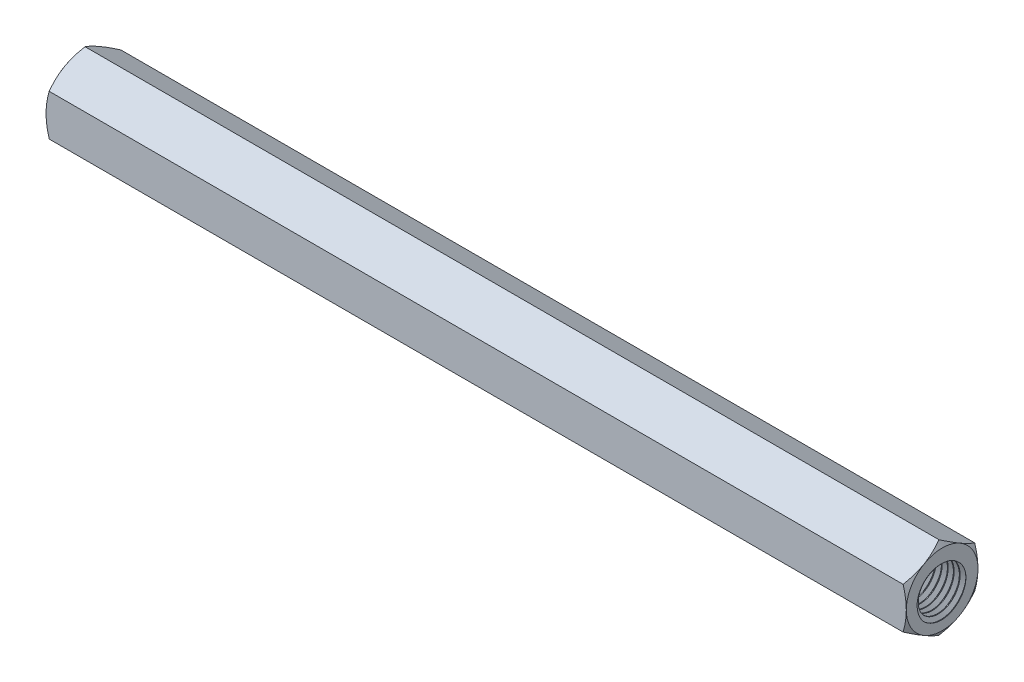
SolidWorks part; units mm, degrees
note: '?' marks a value the reader was unsure of.
ref_plane "Front Plane" through (0, 0, 0) normal (0, 0, 1) x (1, 0, 0)
ref_plane "Top Plane" through (0, 0, 0) normal (0, 1, 0) x (1, 0, 0)
ref_plane "Right Plane" through (0, 0, 0) normal (1, 0, 0) x (0, 0, -1)
sketch "Sketch1" plane through (0, 0, 0) normal (0, 0, 1) x (1, 0, 0)
  line L0 (-76.2, 0) -> (76.2, 0) construction
  line L1 (-76.2, 3.9688) -> (-76.2, -3.9688) construction
  line L2 (76.2, 3.9688) -> (76.2, -3.9688) construction
  line L3 (0, 6.35) -> (0, -6.35) construction
  line L4 (57.15, 3.9688) -> (57.15, -3.9688) construction
  line L5 (-57.15, 3.9688) -> (-57.15, -3.9688) construction
  line L6 (-76.2, 3.9688) -> (-57.15, 3.9688) construction
  line L7 (-76.2, -3.9688) -> (-57.15, -3.9688) construction
  line L8 (57.15, -3.9688) -> (76.2, -3.9688) construction
  line L9 (57.15, 3.9688) -> (76.2, 3.9688) construction
  point P7 (-57.15, 0)
  point P8 (57.15, 0)
  point P17 (67.7333, -3.9688)
  dimension "Length" = 152.4
  dimension "D1" = 19.05
  dimension "Thread Size" = 7.9375
  dimension "Rod OD" = 12.7
  dimension "Thread Length" = 19.05
  dimension "D2" = 114.3
  dimension "D5" = 8.4667
sketch "Sketch2" plane through (0, 0, 0) normal (1, 0, 0) x (0, 0, -1)
  line L1 (6.35, 3.6662) -> (0, 7.3323)
  line L2 (0, 7.3323) -> (-6.35, 3.6662)
  line L3 (-6.35, 3.6662) -> (-6.35, -3.6662)
  line L4 (-6.35, -3.6662) -> (0, -7.3323)
  line L5 (0, -7.3323) -> (6.35, -3.6662)
  line L6 (6.35, -3.6662) -> (6.35, 3.6662)
  circle A1 centre (0, 0) radius 6.35 construction
  point P12 (0, 6.35)
extrude "Boss-Extrude1" add sketch "Sketch2" against normal up to vertex (76.2 mm away) and the other way up to vertex (76.2 mm away) up to point (-76.2, 0, 0) other way up to point (76.2, 0, 0)
sketch "Sketch4" plane through (-76.2, 0, 0) normal (-1, 0, 0) x (0, 0, 1)
  circle A0 centre (0, 0) radius 3.9688
extrude "Cut-Extrude1" cut sketch "Sketch4" against normal up to vertex (19.05 mm away) up to point (-57.15, 0, 0)
sketch "Sketch7" plane through (-57.15, 0, 0) normal (-1, 0, 0) x (0, 0, 1)
  circle A1 centre (0, 0) radius 3.9688
  circle A2 centre (0, 0) radius 3.9688
  dimension "D1" = 0
extrude "Cut-Extrude2" cut sketch "Sketch7" against normal through all draft 59
sketch "Sketch5" plane through (-76.2, 0, 0) normal (-1, 0, 0) x (0, 0, 1)
  line L0 (0, 7.3323) -> (6.35, 3.6662) construction
  circle A0 centre (0, 0) radius 6.35
extrude "Cut-Extrude-Thin2" cut sketch "Sketch5" against normal through all draft 60 thin
mirror "Mirror1" about plane through (0, 0, 0) normal (1, 0, 0) of "Cut-Extrude1", "Cut-Extrude-Thin2", "Cut-Extrude2"
sketch "Sketch3" plane through (-76.2, 0, 0) normal (1, 0, 0) x (0, 0, -1)
  circle A0 centre (0, 0) radius 3.9688 construction
  circle A1 centre (0, 0) radius 3.9688
curve "Helix/Spiral1" pitch 1.0583 height 19.05 turns 18 parameters "pitch"=1.0583
sketch "Sketch6" plane through (0, 0, 0) normal (0, 0, 1) x (1, 0, 0)
  line L0 (-77.1922, 3.8542) -> (-76.1339, 3.8542) construction
  line L1 (-76.1339, 3.8542) -> (-76.663, 4.7707) construction
  line L2 (-76.663, 4.7707) -> (-77.1922, 3.8542) construction
  line L3 (-77.126, 3.9688) -> (-76.2, 3.9688) construction
  line L4 (-76.663, 3.8542) -> (-76.663, 3.9688) construction
  line L5 (-77.1591, 3.9115) -> (-76.1669, 3.9115) construction
  line L6 (-76.7292, 4.6562) -> (-76.5969, 4.6562) construction
  line L7 (-76.663, 4.6562) -> (-76.663, 4.7707) construction
  line L8 (-76.7292, 4.6562) -> (-76.5969, 4.6562) construction
  line L10 (-76.7292, 4.6562) -> (-77.1591, 3.9115)
  line L11 (-77.1591, 3.9115) -> (-76.1669, 3.9115)
  line L12 (-76.1669, 3.9115) -> (-76.5969, 4.6562)
  line L13 (-76.7292, 4.6562) -> (-76.5969, 4.6562)
  point P10 (-76.663, 3.9115)
  dimension "D1" = 1.0583
  dimension "D2" = 0.1323
sweep "Cut-Sweep1" cut profiles "Sketch6" path "Helix/Spiral1"
mirror "Mirror2" about plane through (0, 0, 0) normal (1, 0, 0) of "Cut-Sweep1"
ref_axis "Center Axis 1" through (-84.5766, 0, 0) along (1, 0, 0)?
ref_plane "Contact Plane 1" through (-76.2, 0, 0) normal (-1, 0, 0) x (0, 0, 1)
ref_plane "Contact Plane 2" through (76.2, 0, 0) normal (1, 0, 0) x (0, 0, -1)
equation "\"D1@Sketch1\" = \"Thread Length@Sketch1\""
equation "\"D3@Helix/Spiral1\"=\"Thread Length@Sketch1\""
equation "\"D5@Sketch1\" = \"pitch@Helix/Spiral1\"*8"
equation "\"D1@Sketch6\"=\"pitch@Helix/Spiral1\""
equation "\"D2@Sketch6\"=\"D1@Sketch6\"/ 1/8"
